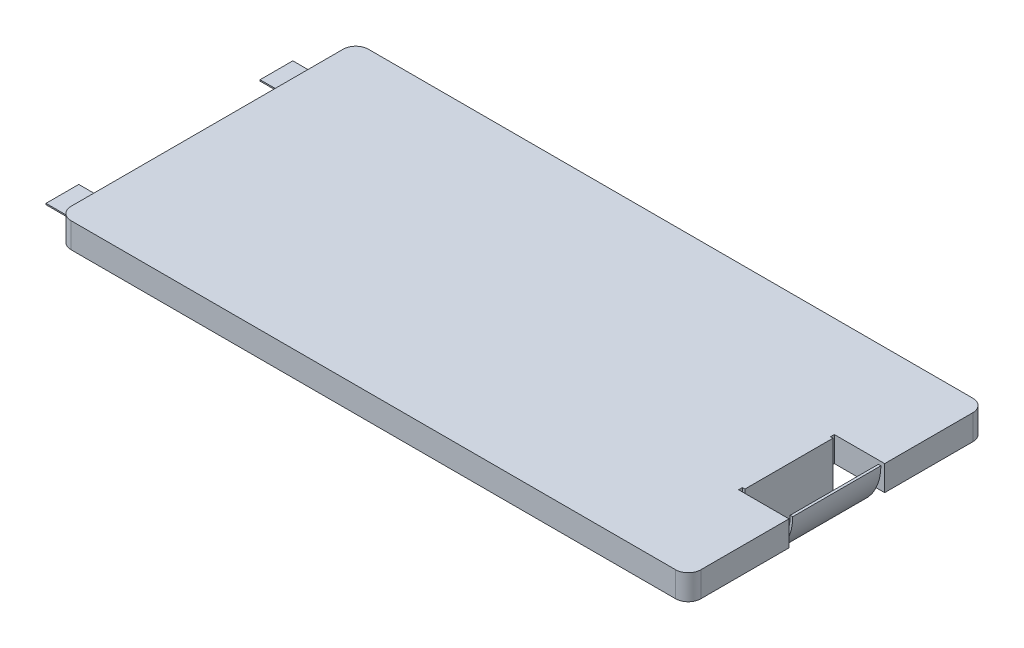
SolidWorks part; units mm, degrees
material "PVB"
ref_plane "Front Plane" through (0, 0, 0) normal (0, 0, 1) x (1, 0, 0)
ref_plane "Top Plane" through (0, 0, 0) normal (0, 1, 0) x (1, 0, 0)
ref_plane "Right Plane" through (0, 0, 0) normal (1, 0, 0) x (0, 0, -1)
ref_axis "X-axis" through (-88.99, 0, 0) along (1, 0, 0)
ref_axis "Y-axis" through (0, 55, 0) along (0, -1, 0)
ref_axis "Z-axis" through (0, 0, -88.99) along (0, 0, 1)
sketch "Sketch1" plane through (0, 0, 0) normal (0, 1, 0) x (1, 0, 0)
  line L1 (-31.75, 14.986) -> (31.75, 14.986)
  line L2 (-31.75, 14.986) -> (-31.75, -14.986)
  line L3 (-31.75, -14.986) -> (31.75, -14.986)
  line L4 (31.75, 14.986) -> (31.75, -14.986)
  line L5 (-31.75, 14.986) -> (31.75, -14.986) construction
  line L6 (-31.75, -14.986) -> (31.75, 14.986) construction
  point P0 (0, 0)
  dimension "D1" = 63.5
  dimension "D2" = 29.972
extrude "Boss-Extrude1" add sketch "Sketch1" along normal blind 2.54
fillet "Fillet1" radius 1.27 4 edges at (-31.75, 1.27, -14.986) (-31.75, 1.27, 14.986) (31.75, 1.27, -14.986) (31.75, 1.27, 14.986)
sketch "Sketch2" plane through (0, 2.54, 0) normal (0, 1, 0) x (1, 0, 0)
  line L0 (31.75, -13.716) -> (31.75, 13.716) construction
  line L1 (36.83, 4.826) -> (26.67, 4.826)
  line L2 (36.83, 4.826) -> (36.83, -4.826)
  line L3 (36.83, -4.826) -> (26.67, -4.826)
  line L4 (26.67, 4.826) -> (26.67, -4.826)
  line L5 (36.83, 4.826) -> (26.67, -4.826) construction
  line L6 (36.83, -4.826) -> (26.67, 4.826) construction
  line L7 (30.48, 14.986) -> (-30.48, 14.986) construction
  point P0 (31.75, 0)
  dimension "D1" = 10.16
  dimension "D2" = 5.08
extrude "Cut-Extrude1" cut sketch "Sketch2" against normal through all
sketch "Sketch3" plane through (0, 0, 0) normal (0, -1, 0) x (1, 0, 0)
  line L0 (26.67, -4.826) -> (26.67, 4.826) construction
  line L1 (29.0566, 3.556) -> (24.2834, 3.556)
  line L2 (29.0566, 3.556) -> (29.0566, -3.556)
  line L3 (29.0566, -3.556) -> (24.2834, -3.556)
  line L4 (24.2834, 3.556) -> (24.2834, -3.556)
  line L5 (29.0566, 3.556) -> (24.2834, -3.556) construction
  line L6 (29.0566, -3.556) -> (24.2834, 3.556) construction
  line L7 (31.75, -4.826) -> (26.67, -4.826) construction
  point P0 (26.67, 0)
  dimension "D1" = 1.27
extrude "Boss-Extrude2" add sketch "Sketch3" along normal blind 2.54 draft 31
sketch "Sketch4" plane through (0, 0, 0) normal (0, 1, 0) x (1, 0, 0)
  line L0 (26.67, 3.556) -> (29.0566, 3.556)
  line L1 (29.0566, 3.556) -> (29.0566, -3.556)
  line L2 (29.0566, -3.556) -> (26.67, -3.556)
  line L3 (26.67, -3.556) -> (26.67, 3.556)
extrude "Cut-Extrude2" cut sketch "Sketch4" against normal through all
sketch "Sketch10" plane through (0, 0, 0) normal (0, 0, 1) x (1, 0, 0)
  line L0 (26.67, 2.54) -> (26.67, -2.54)
  line L1 (26.924, 2.54) -> (26.924, -2.2793)
  line L2 (26.67, 2.54) -> (26.924, 2.54)
  line L3 (31.496, 2.54) -> (31.75, 2.54)
  arc A0 (26.67, -2.54) -> (31.75, 2.54) centre (26.67, 2.54) ccw
  arc A1 (26.924, -2.2793) -> (31.496, 2.54) centre (26.67, 2.54) ccw
  dimension "D1" = 0.254
extrude "Boss-Extrude4" add sketch "Sketch10" along normal mid plane 8.89
sketch "Sketch11" plane through (-31.75, 0, 0) normal (-1, 0, 0) x (0, 0, 1)
  line L0 (-13.716, 0) -> (13.716, 0) construction
  line L1 (9.144, 0) -> (12.446, 0)
  line L2 (9.144, 0) -> (9.144, 0.254)
  line L3 (9.144, 0.254) -> (12.446, 0.254)
  line L4 (12.446, 0) -> (12.446, 0.254)
  line L5 (-14.986, 0) -> (-14.986, 2.54) construction
  line L6 (-12.446, 0) -> (-9.144, 0)
  line L7 (-12.446, 0) -> (-12.446, 0.254)
  line L8 (-12.446, 0.254) -> (-9.144, 0.254)
  line L9 (-9.144, 0) -> (-9.144, 0.254)
  line L10 (14.986, 2.54) -> (14.986, 0) construction
  point P14 (-9.144, 0.4003)
  point P15 (12.446, 0.3243)
  point P16 (9.144, -0.381)
  point P17 (-9.144, 0)
  point P18 (-9.144, 0)
  point P19 (12.446, 0)
  point P20 (12.446, 0.2773)
  point P21 (12.446, 0)
  dimension "D1" = 3.302
  dimension "D2" = 2.54
  dimension "D3" = 2.54
  dimension "D4" = 0.254
extrude "Boss-Extrude5" add sketch "Sketch11" along normal blind 3.81 separate body
sketch "Sketch12" plane through (-31.75, 0, 0) normal (-1, 0, 0) x (0, 0, 1)
  line L0 (-9.144, 0) -> (-9.144, 0.254) construction
  line L1 (-12.446, 0) -> (-9.144, 0)
  line L2 (-12.446, 0) -> (-12.446, 0.127)
  line L3 (-12.446, 0.127) -> (-9.144, 0.127)
  line L4 (-9.144, 0) -> (-9.144, 0.127)
  line L5 (9.144, 0.254) -> (9.144, 0) construction
  line L6 (12.446, 0) -> (9.144, 0)
  line L7 (12.446, 0) -> (12.446, 0.127)
  line L8 (12.446, 0.127) -> (9.144, 0.127)
  line L9 (9.144, 0) -> (9.144, 0.127)
extrude "Cut-Extrude3" cut sketch "Sketch12" along normal through all
